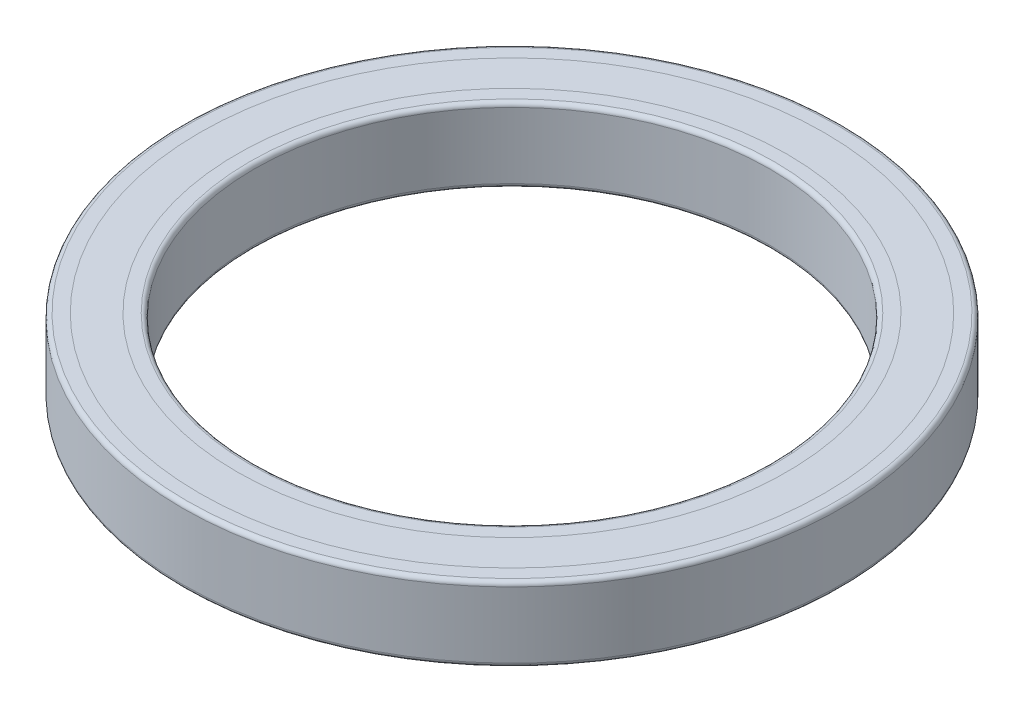
SolidWorks part; units mm, degrees
ref_plane "Front Plane" through (0, 0, 0) normal (0, 0, 1) x (1, 0, 0)
ref_plane "Top Plane" through (0, 0, 0) normal (0, 1, 0) x (1, 0, 0)
ref_plane "Right Plane" through (0, 0, 0) normal (1, 0, 0) x (0, 0, -1)
sketch "Sketch1" plane through (0, 0, 0) normal (0, 0, 1) x (1, 0, 0)
  line L0 (0, 0) -> (0, 17.5281) construction
  line L1 (51.25, 0) -> (0, 0) construction
  line L2 (45, -6.5) -> (57.5, -6.5)
  line L3 (45, -6.5) -> (45, 6.5)
  line L4 (45, 6.5) -> (57.5, 6.5)
  line L5 (57.5, -6.5) -> (57.5, 6.5)
  line L6 (45, -6.5) -> (57.5, 6.5) construction
  line L7 (45, 6.5) -> (57.5, -6.5) construction
  line L8 (48, 6.5) -> (48, 6)
  line L9 (48, 6) -> (54.5, 6)
  line L10 (54.5, 6) -> (54.5, 6.5)
  line L11 (49.25, 2.8723) -> (49.25, 6)
  line L12 (53.25, 2.8723) -> (53.25, 6)
  line L13 (51.25, 0) -> (51.25, 6) construction
  line L14 (48, -6.5) -> (48, -6)
  line L15 (48, -6) -> (54.5, -6)
  line L16 (54.5, -6) -> (54.5, -6.5)
  line L17 (53.25, -2.8723) -> (53.25, -6)
  line L18 (49.25, -2.8723) -> (49.25, -6)
  arc A0 (49.25, 2.8723) -> (49.25, -2.8723) centre (51.25, 0) ccw
  arc A1 (53.25, -2.8723) -> (53.25, 2.8723) centre (51.25, 0) ccw
  point P3 (51.25, 0)
  dimension "D4" = 7
  dimension "D1" = 45
  dimension "D2" = 57.5
  dimension "D3" = 13
  dimension "D5" = 0.5
  dimension "D6" = 3
  dimension "D7" = 4
revolve "Revolve1" add sketch "Sketch1" angle 360 about L0 region at (46.8952, 0, 0) region at (55.6048, 0, 0)
revolve "Revolve2" add sketch "Sketch1<3>" angle 360 about L0 region at (51.25, -6.25, 0) region at (51.25, 6.25, 0)
sketch "Sketch1<3>" plane through (0, 0, 0) normal (0, 0, 1) x (1, 0, 0) same geometry as "Sketch1"
fillet "Fillet1" radius 0.75 2 edges at (0, -6.5, -45) (0, 6.5, -45)
fillet "Fillet2" radius 0.75 2 edges at (0, -6.5, -57.5) (0, 6.5, -57.5)
